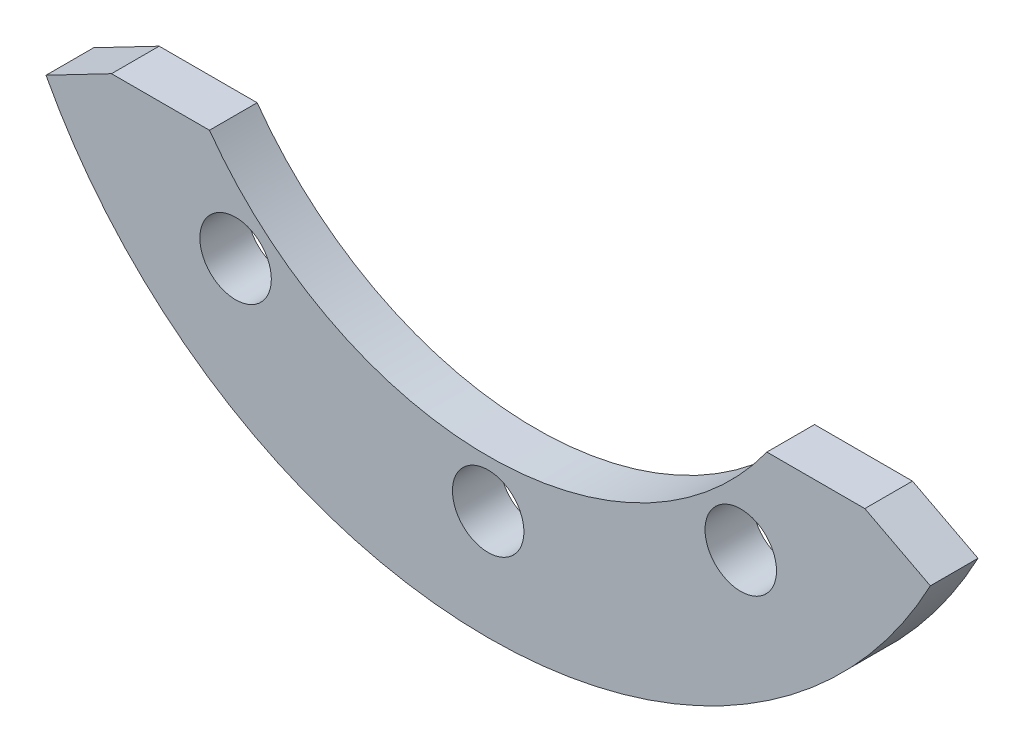
SolidWorks part; units mm, degrees
ref_plane "Front Plane" through (0, 0, 0) normal (0, 0, 1) x (1, 0, 0)
ref_plane "Top Plane" through (0, 0, 0) normal (0, 1, 0) x (1, 0, 0)
ref_plane "Right Plane" through (0, 0, 0) normal (1, 0, 0) x (0, 0, -1)
sketch "Sketch1" plane through (0, 0, 0) normal (0, 0, 1) x (1, 0, 0)
  line L0 (-9.6234, -4.2) -> (-5.8481, -4.2)
  line L1 (5.8481, -4.2) -> (9.6234, -4.2)
  line L3 (0, 0) -> (0, -10.9573) construction
  arc A0 (-5.8481, -4.2) -> (5.8481, -4.2) centre (0, 0) ccw
  arc A1 (-9.6234, -4.2) -> (9.6234, -4.2) centre (0, 0) ccw
  dimension "D1" = 10.5
  dimension "D2" = 7.2
  dimension "D3" = 6.3
extrude "Boss-Extrude1" add sketch "Sketch1" against normal blind 1
hole_wizard "Ø1.5 (1.5) Diameter Hole1" positions "Sketch9" profile "Sketch8" hole size "Ø1.5" standard "DIN" end condition up to next
sketch "Sketch9" plane through (0, 0, 0) normal (0, 0, 1) x (1, 0, 0)
  line L0 (0, 0) -> (0, -8.2) construction
  circle A0 centre (0, 0) radius 8.2 construction
  point P5 (0, -8.2)
  point P7 (-5.3, -6.257)
  point P9 (5.3, -6.257)
  dimension "D1" = 16.4
  dimension "D2" = 10.6
sketch "Sketch8" plane through (0, -8.2, 0) normal (1, 0, 0) x (0, -1, 0)
  line L0 (0, 0) -> (0, 1)
  line L1 (0, 1) -> (0.75, 1)
  line L2 (0.75, 1) -> (0.75, 0)
  line L5 (0.75, 0) -> (0, 0)
  line L11 (0, -6.35) -> (0, 107.95) construction
  dimension "Thru Hole Dia." = 1.5
  dimension "Thru Hole Depth" = 1
sketch "Sketch2" plane through (0, 0, 0) normal (0, 0, 1) x (1, 0, 0)
  line L0 (-7.9033, -4.2) -> (-9.2782, -4.9157)
  line L1 (0, 0) -> (0, -10.5) construction
  line L2 (-5.8481, -4.2) -> (-9.6234, -4.2) construction
  line L3 (-7.9033, -4.2) -> (-9.6234, -4.2)
  arc A0 (-9.6234, -4.2) -> (9.6234, -4.2) centre (0, 0) ccw construction
  arc A1 (-9.6234, -4.2) -> (-9.2782, -4.9157) centre (0, 0) ccw
  circle A2 centre (0, 0) radius 8.95 construction
  circle A4 centre (0, 0) radius 8.2 construction
  circle A5 centre (-5.3, -6.257) radius 0.75 construction
  dimension "D3" = 16.4
  dimension "D1" = 62.5
extrude "Cut-Extrude2" cut sketch "Sketch2" against normal through all
mirror "Mirror1" about plane through (0, 0, 0) normal (1, 0, 0) of "Cut-Extrude2"
